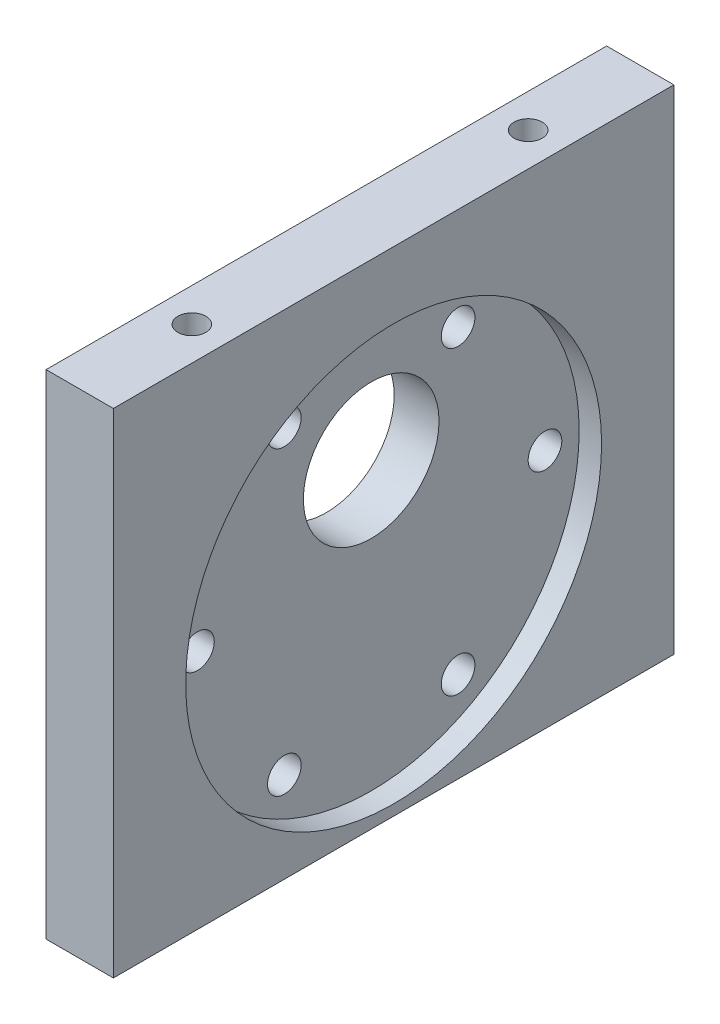
SolidWorks part; units mm, degrees
material "1060 Alloy"
ref_plane "Front Plane" through (0, 0, 0) normal (0, 0, 1) x (1, 0, 0)
ref_plane "Top Plane" through (0, 0, 0) normal (0, 1, 0) x (1, 0, 0)
ref_plane "Right Plane" through (0, 0, 0) normal (1, 0, 0) x (0, 0, -1)
sketch "Sketch1" plane through (0, 0, 0) normal (0, 1, 0) x (1, 0, 0)
  line L1 (0, 0) -> (6, 0)
  line L2 (0, 0) -> (0, 50)
  line L3 (0, 50) -> (6, 50)
  line L4 (6, 0) -> (6, 50)
  dimension "D1" = 50
  dimension "D2" = 6
extrude "Boss-Extrude1" add sketch "Sketch1" along normal blind 44
hole_wizard "Tap Drill for M3 Tap1" positions "Sketch3" profile "Sketch2" hole size "M3" standard "ISO"
sketch "Sketch3" plane through (0, 44, 0) normal (0, 1, 0) x (-1, 0, 0)
  line L0 (0, 0) -> (-6, 0) construction
  line L1 (-6, 0) -> (-6, -50) construction
  line L2 (-6, -50) -> (0, -50) construction
  point P0 (-3, -10)
  point P1 (-3, -40)
  point P6 (-3, -50)
  dimension "D1" = 10
  dimension "D2" = 3
  dimension "D3" = 10
sketch "Sketch2" plane through (3, 44, -10) normal (1, 0, 0) x (0, 0, 1)
  line L0 (0, 0) -> (0, 10.7511)
  line L1 (0, 10.7511) -> (1.25, 10)
  line L2 (1.25, 10) -> (1.25, 0)
  line L5 (1.25, 0) -> (0, 0)
  line L10 (0, 10.7511) -> (-1.25, 10) construction
  line L11 (0, -6.35) -> (0, 107.95) construction
  dimension "Hole Dia." = 2.5
  dimension "Hole Depth" = 10
  dimension "Drill Angle" = 118
hole_wizard "Tap Drill for M3 Tap2" positions "Sketch5" profile "Sketch4" hole size "M3" standard "ISO"
sketch "Sketch5" plane through (0, 0, 0) normal (0, -1, 0) x (1, 0, 0)
  line L0 (6, 0) -> (6, -50) construction
  line L1 (0, 0) -> (6, 0) construction
  line L2 (6, -50) -> (0, -50) construction
  point P0 (3, -10)
  point P1 (3, -40)
  dimension "D1" = 3
  dimension "D2" = 10
  dimension "D3" = 10
sketch "Sketch4" plane through (3, 0, -10) normal (1, 0, 0) x (0, 0, -1)
  line L0 (0, 0) -> (0, 7.7511)
  line L1 (0, 7.7511) -> (1.25, 7)
  line L2 (1.25, 7) -> (1.25, 0)
  line L5 (1.25, 0) -> (0, 0)
  line L10 (0, 7.7511) -> (-1.25, 7) construction
  line L11 (0, -6.35) -> (0, 107.95) construction
  dimension "Hole Dia." = 2.5
  dimension "Hole Depth" = 7
  dimension "Drill Angle" = 118
sketch "Sketch6" plane through (6, 0, 0) normal (1, 0, 0) x (0, 0, -1)
  line L0 (0, 44) -> (0, 0) construction
  line L1 (0, 0) -> (50, 0) construction
  circle A0 centre (25, 19.5) radius 18.55
  dimension "D2" = 37.1
  dimension "D1" = 25
  dimension "D3" = 19.5
extrude "Cut-Extrude1" cut sketch "Sketch6" against normal blind 2
sketch "Sketch7" plane through (4, 0, 0) normal (1, 0, 0) x (0, 0, -1)
  line L1 (6.45, 19.5) -> (25, 19.5) construction
  circle A0 centre (25, 26.5) radius 6.05
  circle A1 centre (25, 19.5) radius 18.55 construction
  circle A3 centre (9.5, 19.5) radius 1.5
  circle A4 centre (25, 19.5) radius 18.55 construction
  dimension "D1" = 12.1
  dimension "D4" = 3
  dimension "D2" = 25
  dimension "D3" = 7
  dimension "D5" = 15.5
extrude "Cut-Extrude2" cut sketch "Sketch7" against normal up to next
pattern_circular "CirPattern1" count 6 over 360 about axis through (6, 19.5, -25) along (1, 0, 0) of face at (4, 19.5, -11)
chamfer "Chamfer1" distance 1.4 angle 45 6 edges at (0, 19.5, -39) (0, 7.3756, -32) (0, 7.3756, -18) (0, 19.5, -11) (0, 31.6244, -18) (0, 31.6244, -32)
